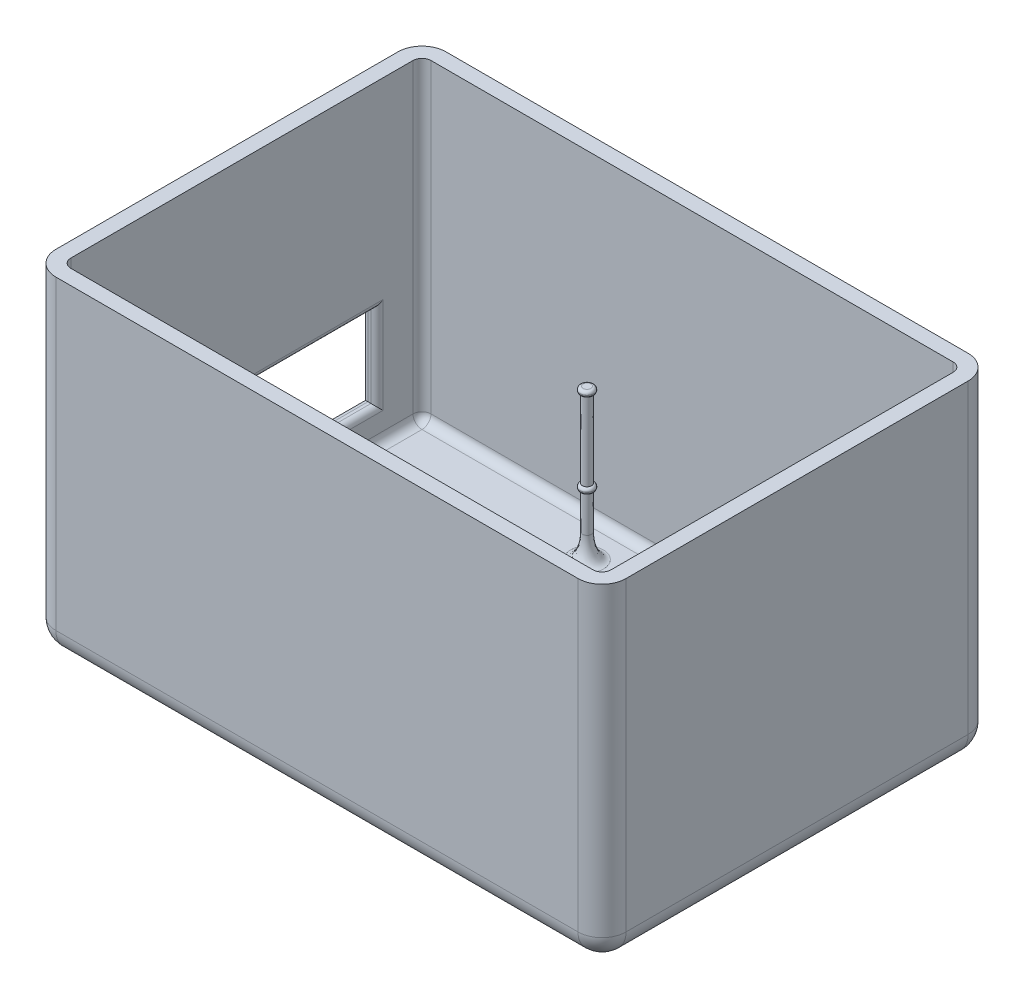
SolidWorks part; units mm, degrees
ref_plane "Front Plane" through (0, 0, 0) normal (0, 0, 1) x (1, 0, 0)
ref_plane "Top Plane" through (0, 0, 0) normal (0, 1, 0) x (1, 0, 0)
ref_plane "Right Plane" through (0, 0, 0) normal (1, 0, 0) x (0, 0, -1)
sketch "Sketch2" plane through (0, 0, 0) normal (0, 1, 0) x (1, 0, 0)
  line L1 (0, 0) -> (95, 0)
  line L2 (0, 0) -> (0, 65)
  line L3 (0, 65) -> (95, 65)
  line L4 (95, 0) -> (95, 65)
  dimension "D1" = 95
  dimension "D2" = 65
extrude "Boss-Extrude1" add sketch "Sketch2" along normal blind 55
fillet "Fillet2" radius 4 8 edges at (0, 27.5, 0) (0, 0, -32.5) (0, 27.5, -65) (47.5, 0, -65) (95, 27.5, -65) (47.5, 0, 0) (95, 0, -32.5) (95, 27.5, 0)
shell "Shell1" thickness 2.5 removed face at (47.5, 55, -32.5)
sketch "Sketch10" plane through (0, 2.5, 0) normal (0, 1, 0) x (1, 0, 0)
  line L0 (87.5, 62.5) -> (87.5, 2.5) construction
  line L1 (91, 62.5) -> (4, 62.5) construction
  line L2 (2.5, 2.5) -> (92.5, 2.5) construction
  line L3 (92.5, 2.5) -> (92.5, 62.5) construction
  line L4 (92.5, 56) -> (2.5, 56) construction
  line L6 (2.5, 62.5) -> (2.5, 2.5) construction
  circle A0 centre (87.5, 12.5) radius 0.75
  circle A1 centre (87.5, 40.5) radius 0.75
  circle A2 centre (36.5, 56) radius 0.75
  dimension "D6" = 1.5
  dimension "D7" = 1.5
  dimension "D8" = 1.5
  dimension "D1" = 10
  dimension "D2" = 5
  dimension "D3" = 28
  dimension "D4" = 15.5
  dimension "D5" = 51
extrude "Boss-Extrude2" add sketch "Sketch10" along normal blind 25
fillet "Fillet3" radius 2 3 edges at (87.5, 2.5, -13.25) (87.5, 2.5, -41.25) (36.5, 2.5, -56.75) second distance 4 tangent propagation no first distance on face at (36.5, 2.5, -56.75)
ref_plane "Plane2" through (0, 12.5, 0) normal (0, -1, 0) x (-1, 0, 0)
sketch "Sketch12" plane through (0, 12.5, 0) normal (0, -1, 0) x (-1, 0, 0)
  circle A0 centre (-36.5, 56) radius 1.15
  circle A1 centre (-87.5, 40.5) radius 1.15
  circle A2 centre (-87.5, 12.5) radius 1.15
  dimension "D1" = 2.3
  dimension "D2" = 2.3
  dimension "D3" = 2.3
extrude "Boss-Extrude3" add sketch "Sketch12" against normal blind 1
ref_plane "Plane4" through (0, 27.5, 0) normal (0, -1, 0) x (-1, 0, 0)
sketch "Sketch14" plane through (0, 27.5, 0) normal (0, -1, 0) x (-1, 0, 0)
  circle A0 centre (-36.5, 56) radius 1.15
  circle A1 centre (-87.5, 40.5) radius 1.15
  circle A2 centre (-87.5, 12.5) radius 1.15
  dimension "D1" = 2.3
  dimension "D2" = 2.3
  dimension "D3" = 2.3
extrude "Boss-Extrude4" add sketch "Sketch14" along normal blind 1
fillet "Fillet4" radius 0.5 12 edges at (37.65, 12.5, -56) (37.65, 13.5, -56) (88.65, 12.5, -40.5) (88.65, 13.5, -40.5) (88.65, 26.5, -40.5) (88.65, 27.5, -40.5) (88.65, 26.5, -12.5) (88.65, 27.5, -12.5) (88.65, 12.5, -12.5) (88.65, 13.5, -12.5) (37.65, 26.5, -56) (37.65, 27.5, -56)
sketch "Sketch16" plane through (0, 0, 0) normal (-1, 0, 0) x (0, 0, 1)
  line L0 (-61, 8) -> (-4, 8) construction
  line L1 (-61, 55) -> (-61, 4) construction
  line L2 (-4, 4) -> (-4, 55) construction
  line L3 (-61, 4) -> (-4, 4) construction
  line L5 (-55, 8) -> (-10, 8)
  line L6 (-55, 8) -> (-55, 22)
  line L7 (-55, 22) -> (-10, 22)
  line L8 (-10, 8) -> (-10, 22)
  dimension "D1" = 4
  dimension "D2" = 14
  dimension "D3" = 6
  dimension "D4" = 6
extrude "Cut-Extrude1" cut sketch "Sketch16" against normal blind 4
fillet "Fillet5" radius 1 8 edges at (2.5, 15, -55) (0, 15, -55) (2.5, 22, -32.5) (0, 22, -32.5) (2.5, 8, -32.5) (0, 8, -32.5) (2.5, 15, -10) (0, 15, -10)
